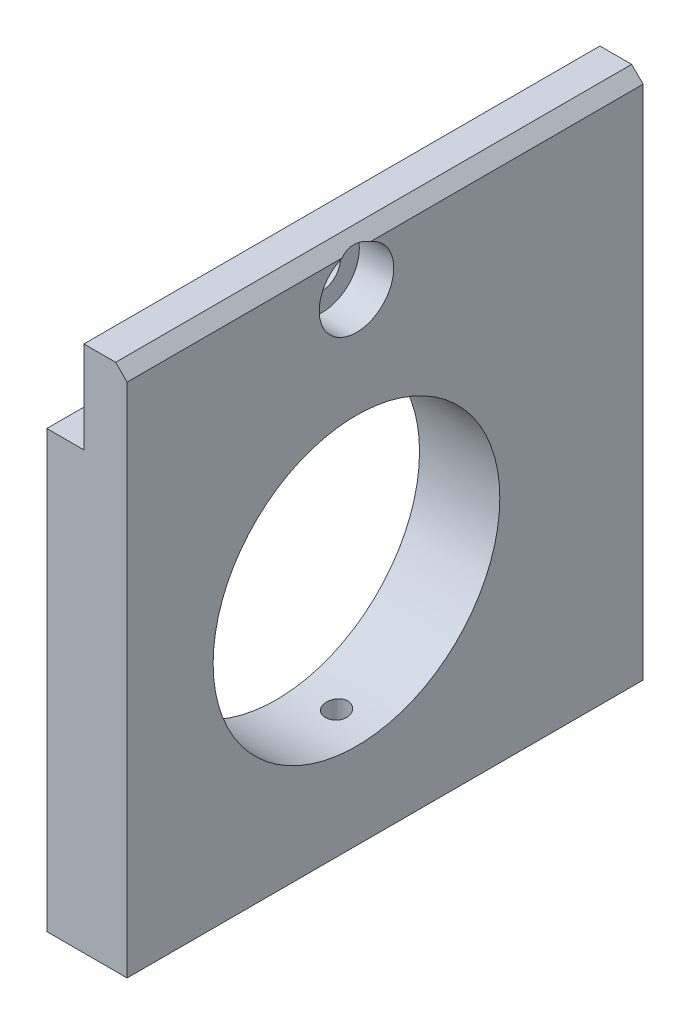
SolidWorks part; units mm, degrees
material "6061-T6 (SS)"
ref_plane "Front" through (0, 0, 0) normal (0, 0, 1) x (1, 0, 0)
ref_plane "Top" through (0, 0, 0) normal (0, 1, 0) x (1, 0, 0)
ref_plane "Right" through (0, 0, 0) normal (1, 0, 0) x (0, 0, -1)
sketch "Sketch1" plane through (0, 0, 0) normal (0, 0, 1) x (1, 0, 0)
  line L2 (3.23, 30.3627) -> (3.23, 22.3627)
  line L3 (3.23, 22.3627) -> (0, 22.3627)
  line L4 (0, 22.3627) -> (0, -15.6373)
  line L5 (0, -15.6373) -> (7, -15.6373)
  line L6 (7, -15.6373) -> (7, 30.3627)
  line L8 (3.23, 30.3627) -> (7, 30.3627)
  dimension "D1" = 8
  dimension "D2" = 7
  dimension "D3" = 38
  dimension "D4" = 3.77
extrude "Boss-Extrude1" add sketch "Sketch1" along normal blind 45
hole_wizard "CBORE for M3 SHCS1" positions "Sketch2" profile "Sketch3" counterbore size "M3" standard "ANSI Metric" end condition through all
sketch "Sketch2" plane through (7, 0, 0) normal (1, 0, 0) x (0, 0, -1)
  line L1 (0, -15.6373) -> (0, 30.3627) construction
  line L2 (-45, 22.3627) -> (0, 22.3627) construction
  point P0 (-25, 26.3627)
  dimension "D1" = 4
  dimension "D2" = 25
sketch "Sketch3" plane through (7, 26.3627, 25) normal (0, 1, 0) x (0, 0, -1)
  line L0 (0, 0) -> (0, 7)
  line L1 (0, 7) -> (1.6, 7)
  line L3 (1.6, 7) -> (1.6, 3)
  line L4 (1.6, 3) -> (3.25, 3)
  line L5 (3.25, 3) -> (3.25, 0)
  line L7 (3.25, 0) -> (0, 0)
  line L11 (0, -6.35) -> (0, 107.95) construction
  dimension "Thru Hole Dia." = 3.2
  dimension "Thru Hole Depth" = 7
  dimension "C'Bore Dia." = 6.5
  dimension "C'Bore Depth" = 3
hole_wizard "Ø25.0 (25) Diameter Hole1" positions "Sketch4" profile "Sketch5" hole size "Ø25.0" standard "ANSI Metric" end condition up to next
sketch "Sketch4" plane through (7, 0, 0) normal (1, 0, 0) x (0, 0, -1)
  line L1 (-45, -15.6373) -> (0, -15.6373) construction
  line L2 (-45, -15.6373) -> (-45, 30.3627) construction
  point P0 (-25, 4.3627)
  dimension "D1" = 20
  dimension "D2" = 20
sketch "Sketch5" plane through (7, 4.3627, 25) normal (0, 1, 0) x (0, 0, -1)
  line L0 (0, 0) -> (0, 7)
  line L1 (0, 7) -> (12.5, 7)
  line L2 (12.5, 7) -> (12.5, 0)
  line L5 (12.5, 0) -> (0, 0)
  line L11 (0, -6.35) -> (0, 107.95) construction
  dimension "Thru Hole Dia." = 25
  dimension "Thru Hole Depth" = 7
chamfer "Chamfer1" distance 1 angle 45 1 edges at (7, 30.3627, 22.5)
hole_wizard "Ø3.0mm Dowel Hole1" positions "Sketch6" profile "Sketch7" hole size "Ø3.0" standard "ANSI Metric"
sketch "Sketch6" plane through (0, -15.6373, 0) normal (0, -1, 0) x (-1, 0, 0)
  line L0 (0, -45) -> (-7, -45) construction
  line L1 (0, 0) -> (-7, 0) construction
  line L2 (0, -45) -> (0, 0) construction
  point P0 (-3.5, -38)
  point P2 (-3.5, -7)
  dimension "D1" = 7
  dimension "D2" = 7
  dimension "D3" = 3.5
sketch "Sketch7" plane through (3.5, -15.6373, 38) normal (1, 0, 0) x (0, 0, -1)
  line L0 (0, 0) -> (0, 5.4013)
  line L1 (0, 5.4013) -> (1.5, 4.5)
  line L2 (1.5, 4.5) -> (1.5, 0)
  line L5 (1.5, 0) -> (0, 0)
  line L10 (0, 5.4013) -> (-1.5, 4.5) construction
  line L11 (0, -6.35) -> (0, 107.95) construction
  dimension "Hole Dia." = 3
  dimension "Hole Depth" = 4.5
  dimension "Drill Angle" = 118
hole_wizard "M3x0.5 Tapped Hole1" positions "Sketch8" profile "Sketch9" tap size "M3x0.5" standard "ANSI Metric"
sketch "Sketch8" plane through (0, -15.6373, 0) normal (0, -1, 0) x (-1, 0, 0)
  line L0 (0, -45) -> (0, 0) construction
  line L1 (0, -45) -> (-7, -45) construction
  point P0 (-3.5, -23)
  dimension "D1" = 3.5
  dimension "D2" = 22
sketch "Sketch9" plane through (3.5, -15.6373, 23) normal (1, 0, 0) x (0, 0, -1)
  line L0 (0, 0) -> (0, 8.2511)
  line L1 (0, 8.2511) -> (1.25, 7.5)
  line L2 (1.25, 7.5) -> (1.25, 0)
  line L5 (1.25, 0) -> (0, 0)
  line L10 (0, 8.2511) -> (-1.25, 7.5) construction
  line L11 (0, -6.35) -> (0, 107.95) construction
  dimension "Tap Drill Dia." = 2.5
  dimension "Tap Drill Depth" = 7.5
  dimension "Drill Angle" = 118
cosmetic thread "Hole Thread1" parameters "D1"=6, "D2"=3
